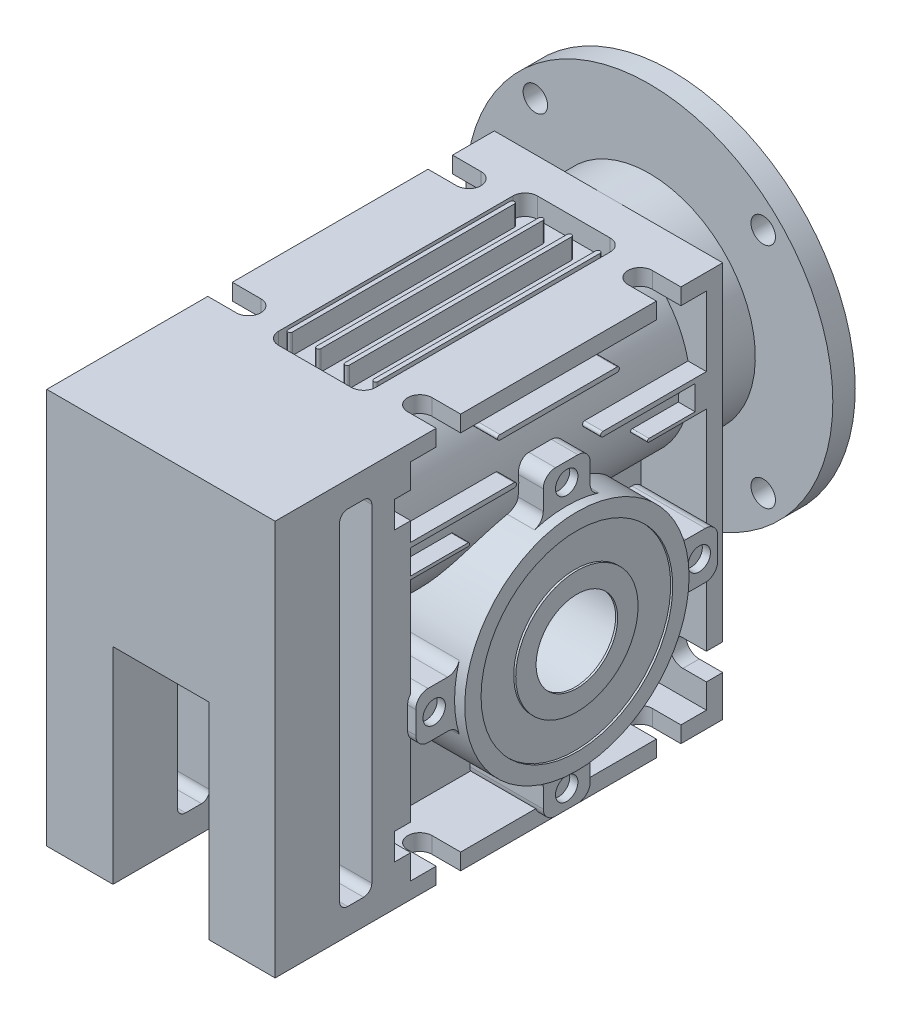
SolidWorks part; units mm, degrees
ref_plane "Front Plane" through (0, 0, 0) normal (0, 0, 1) x (1, 0, 0)
ref_plane "Top Plane" through (0, 0, 0) normal (0, 1, 0) x (1, 0, 0)
ref_plane "Right Plane" through (0, 0, 0) normal (1, 0, 0) x (0, 0, -1)
sketch "Sketch1" plane through (0, 0, 0) normal (1, 0, 0) x (0, 0, -1)
  line L1 (-40.25, -48.5) -> (40.25, -48.5)
  line L2 (-40.25, -48.5) -> (-40.25, 48.5)
  line L3 (-40.25, 48.5) -> (40.25, 48.5)
  line L4 (40.25, -48.5) -> (40.25, 48.5)
  line L5 (-40.25, -48.5) -> (40.25, 48.5) construction
  line L6 (-40.25, 48.5) -> (40.25, -48.5) construction
  point P0 (0, 0)
  dimension "D1" = 97
  dimension "D2" = 80.5
extrude "Boss-Extrude1" add sketch "Sketch1" along normal mid plane 56
sketch "Sketch2" plane through (0, 0, 0) normal (1, 0, 0) x (0, 0, -1)
  line L0 (-40.25, -48.5) -> (40.25, -48.5) construction
  circle A0 centre (0, -9.5) radius 27.5
  point P2 (0, -37)
  dimension "D2" = 55
  dimension "D1" = 11.5
extrude "Boss-Extrude2" add sketch "Sketch2" along normal mid plane 65
sketch "Sketch3" plane through (28, 0, 0) normal (1, 0, 0) x (0, 0, -1)
  line L0 (-29.2179, -15.25) -> (-34, -15.25)
  line L2 (-5.75, -38.7179) -> (-5.75, -43.5)
  line L3 (-2.75, -46.5) -> (2.75, -46.5)
  line L4 (5.75, -38.7179) -> (5.75, -43.5)
  line L5 (-5.75, 27.5) -> (5.75, -46.5) construction
  line L6 (-5.75, -46.5) -> (5.75, 27.5) construction
  line L7 (-37, -6.75) -> (-37, -12.25)
  line L8 (-29.2179, -3.75) -> (-34, -3.75)
  line L9 (-5.75, 19.7179) -> (-5.75, 24.5)
  line L10 (2.75, 27.5) -> (-2.75, 27.5)
  line L11 (5.75, 19.7179) -> (5.75, 24.5)
  line L12 (29.2179, -3.75) -> (34, -3.75)
  line L13 (37, -12.25) -> (37, -6.75)
  line L14 (29.2179, -15.25) -> (34, -15.25)
  arc A0 (-5.75, -43.5) -> (-2.75, -46.5) centre (-2.75, -43.5) ccw
  circle A1 centre (0, -9.5) radius 27.5
  arc A2 (7.8893, -35.844) -> (-7.8893, -35.844) centre (0, -9.5) ccw
  arc A3 (2.75, -46.5) -> (5.75, -43.5) centre (2.75, -43.5) ccw
  arc A4 (7.8893, -35.844) -> (5.75, -38.7179) centre (8.75, -38.7179) ccw
  arc A5 (-7.8893, -35.844) -> (-5.75, -38.7179) centre (-8.75, -38.7179) cw
  circle A6 centre (0, -42) radius 2.75
  arc A7 (-26.344, -17.3893) -> (-29.2179, -15.25) centre (-29.2179, -18.25) ccw
  arc A8 (-37, -12.25) -> (-34, -15.25) centre (-34, -12.25) ccw
  arc A9 (-34, -3.75) -> (-37, -6.75) centre (-34, -6.75) ccw
  arc A10 (-26.344, -1.6107) -> (-29.2179, -3.75) centre (-29.2179, -0.75) cw
  circle A11 centre (-32.5, -9.5) radius 2.75
  arc A12 (-7.8893, 16.844) -> (-5.75, 19.7179) centre (-8.75, 19.7179) ccw
  arc A13 (-2.75, 27.5) -> (-5.75, 24.5) centre (-2.75, 24.5) ccw
  arc A14 (5.75, 24.5) -> (2.75, 27.5) centre (2.75, 24.5) ccw
  arc A15 (7.8893, 16.844) -> (5.75, 19.7179) centre (8.75, 19.7179) cw
  circle A16 centre (0, 23) radius 2.75
  arc A17 (26.344, -1.6107) -> (29.2179, -3.75) centre (29.2179, -0.75) ccw
  arc A18 (37, -6.75) -> (34, -3.75) centre (34, -6.75) ccw
  arc A19 (34, -15.25) -> (37, -12.25) centre (34, -12.25) ccw
  arc A20 (26.344, -17.3893) -> (29.2179, -15.25) centre (29.2179, -18.25) cw
  circle A21 centre (32.5, -9.5) radius 2.75
  point P65 (0, -9.5)
  circle M5 centre (0, -9.5) radius 27.5
  dimension "D4" = 3
  dimension "D5" = 3
  dimension "D6" = 3
  dimension "D7" = 5.5
  dimension "D2" = 11.5
  dimension "D3" = 37
  dimension "D8" = 32.5
  dimension "D9" = 5.75
  dimension "D1" = 0
  dimension "D10" = 4
extrude "Boss-Extrude3" add sketch "Sketch3" along normal blind 2 contours A2 A10 L8 A9 L7 A8 L0 A7 A11 | A2 A15 L11 A14 L10 A13 L9 A12 A16 | A2 A20 L14 A19 L13 A18 L12 A17 A21 | A5 L2 A0 L3 A3 L4 A4 A6 M5 region at (28, -15.0596, 31.609) region at (28, -37.1904, 0) region at (28, 17.8129, 6.1908) region at (28, -13.5144, -27.3979)
mirror "Mirror1" about plane through (0, 0, 0) normal (1, 0, 0) of "Boss-Extrude3"
sketch "Sketch4" plane through (0, 0, -40.25) normal (0, 0, -1) x (-1, 0, 0)
  line L0 (-28, 48.5) -> (28, 48.5) construction
  circle A0 centre (0, 22.5) radius 26
  dimension "D1" = 52
extrude "Boss-Extrude4" add sketch "Sketch4" along normal blind 10
sketch "Sketch7" plane through (0, 0, -50.25) normal (0, 0, -1) x (-1, 0, 0)
  circle A0 centre (0, 22.5) radius 45
  dimension "D1" = 90
extrude "Boss-Extrude5" add sketch "Sketch7" along normal blind 5.5
sketch "Sketch8" plane through (0, 0, 0) normal (1, 0, 0) x (0, 0, -1)
  line L0 (55.75, 53) -> (52.75, 53)
  line L1 (55.75, -22.5) -> (55.75, 67.5) construction
  line L2 (52.75, 53) -> (52.75, 46.5)
  line L3 (52.75, 46.5) -> (45.75, 46.5)
  line L4 (45.75, 46.5) -> (45.75, 32.5)
  line L5 (45.75, 32.5) -> (50.75, 32.5)
  line L6 (50.75, 32.5) -> (50.75, 28)
  line L7 (50.75, 28) -> (22.75, 28)
  line L8 (22.75, 28) -> (22.75, 22.5)
  line L9 (22.75, 22.5) -> (55.75, 22.5)
  line L10 (55.75, 22.5) -> (55.75, 53)
  line L11 (55.75, 67.5) -> (50.25, 67.5) construction
  dimension "D1" = 14.5
  dimension "D2" = 3
  dimension "D3" = 7
  dimension "D4" = 24
  dimension "D5" = 5.5
  dimension "D6" = 28
  dimension "D7" = 5
  dimension "D8" = 10
revolve "Cut-Revolve1" cut sketch "Sketch8" angle 360 about L9
sketch "Sketch9" plane through (0, 0, -55.75) normal (0, 0, -1) x (-1, 0, 0)
  line L0 (0, 22.5) -> (0, 67.5) construction
  line L1 (0, 22.5) -> (27.9307, 50.4307) construction
  circle A2 centre (27.9307, 50.4307) radius 3
  circle A3 centre (27.9307, -5.4307) radius 3
  circle A4 centre (-27.9307, -5.4307) radius 3
  circle A5 centre (-27.9307, 50.4307) radius 3
  circle A6 centre (0, 22.5) radius 45 construction
  point P18 (0, 22.5)
  dimension "D1" = 6
  dimension "D3" = 45
  dimension "D4" = 39.5
  dimension "D2" = 4
extrude "Cut-Extrude1" cut sketch "Sketch9" against normal blind 5.5 contours A2 | A3 | A4 | A5
sketch "Sketch10" plane through (-28, 0, 0) normal (-1, 0, 0) x (0, 0, 1)
  line L4 (-40.25, 48.5) -> (-40.25, -48.5)
  line L5 (-40.25, -48.5) -> (40.25, -48.5)
  line L6 (40.25, -48.5) -> (40.25, 48.5)
  line L7 (40.25, 48.5) -> (-40.25, 48.5)
  line L8 (-40.25, 48.5) -> (-40.25, -48.5)
  line L9 (-40.25, -48.5) -> (40.25, -48.5)
  line L10 (40.25, -48.5) -> (40.25, 48.5)
  line L11 (40.25, 48.5) -> (-40.25, 48.5)
  line L12 (29.2179, -3.75) -> (34, -3.75) construction
  line L13 (37, -6.75) -> (37, -12.25) construction
  line L14 (29.2179, -15.25) -> (34, -15.25) construction
  line L15 (5.75, -38.7179) -> (5.75, -43.5) construction
  line L16 (2.75, -46.5) -> (-2.75, -46.5) construction
  line L17 (-5.75, -38.7179) -> (-5.75, -43.5) construction
  line L18 (-29.2179, -15.25) -> (-34, -15.25) construction
  line L19 (-37, -12.25) -> (-37, -6.75) construction
  line L20 (-29.2179, -3.75) -> (-34, -3.75) construction
  line L21 (-5.75, 19.7179) -> (-5.75, 24.5) construction
  line L22 (-2.75, 27.5) -> (2.75, 27.5) construction
  line L23 (5.75, 19.7179) -> (5.75, 24.5) construction
  line L24 (29.2179, -3.75) -> (34, -3.75)
  line L25 (37, -6.75) -> (37, -12.25)
  line L26 (29.2179, -15.25) -> (34, -15.25)
  line L27 (5.75, -38.7179) -> (5.75, -43.5)
  line L28 (2.75, -46.5) -> (-2.75, -46.5)
  line L29 (-5.75, -38.7179) -> (-5.75, -43.5)
  line L30 (-29.2179, -15.25) -> (-34, -15.25)
  line L31 (-37, -12.25) -> (-37, -6.75)
  line L32 (-29.2179, -3.75) -> (-34, -3.75)
  line L33 (-5.75, 19.7179) -> (-5.75, 24.5)
  line L34 (-2.75, 27.5) -> (2.75, 27.5)
  line L35 (5.75, 19.7179) -> (5.75, 24.5)
  line L36 (36.25, 44.5) -> (-36.25, 44.5)
  line L37 (-36.25, 44.5) -> (-36.25, -44.5)
  line L38 (-36.25, -44.5) -> (36.25, -44.5)
  line L39 (36.25, -44.5) -> (36.25, 44.5)
  line L40 (-14.3534, 38.7414) -> (14.3534, 38.7414) construction
  line L41 (-14.3534, 39.3275) -> (14.3534, 39.3275)
  line L42 (-14.3534, 38.1553) -> (14.3534, 38.1553)
  line L43 (-10.8913, 26.8155) -> (-36.25, 26.8155) construction
  line L44 (-10.8913, 26.2345) -> (-36.25, 26.2345)
  line L45 (-10.8913, 27.3965) -> (-36.25, 27.3965)
  line L46 (-22.1859, 19.851) -> (-36.25, 19.851) construction
  line L47 (-22.1859, 19.4507) -> (-36.25, 19.4507)
  line L48 (-22.1859, 20.2512) -> (-36.25, 20.2512)
  line L49 (0, 25.75) -> (0, 0)
  line L50 (36.25, 44.5) -> (36.25, -44.5)
  line L51 (22.1859, 19.851) -> (36.25, 19.851) construction
  line L52 (22.1859, 19.4507) -> (36.25, 19.4507)
  line L53 (22.1859, 20.2512) -> (36.25, 20.2512)
  line L54 (10.8913, 26.8155) -> (36.25, 26.8155) construction
  line L55 (10.8913, 26.2345) -> (36.25, 26.2345)
  line L56 (10.8913, 27.3965) -> (36.25, 27.3965)
  line L57 (-33.4862, 26.2345) -> (-33.4862, 20.2512)
  arc A0 (26.344, -1.6107) -> (29.2179, -3.75) centre (29.2179, -0.75) ccw construction
  arc A1 (37, -6.75) -> (34, -3.75) centre (34, -6.75) ccw construction
  arc A2 (34, -15.25) -> (37, -12.25) centre (34, -12.25) ccw construction
  arc A3 (29.2179, -15.25) -> (26.344, -17.3893) centre (29.2179, -18.25) ccw construction
  arc A4 (7.8893, -35.844) -> (26.344, -17.3893) centre (0, -9.5) ccw construction
  arc A5 (7.8893, -35.844) -> (5.75, -38.7179) centre (8.75, -38.7179) ccw construction
  arc A6 (2.75, -46.5) -> (5.75, -43.5) centre (2.75, -43.5) ccw construction
  arc A7 (-5.75, -43.5) -> (-2.75, -46.5) centre (-2.75, -43.5) ccw construction
  arc A8 (-5.75, -38.7179) -> (-7.8893, -35.844) centre (-8.75, -38.7179) ccw construction
  arc A9 (-26.344, -17.3893) -> (-7.8893, -35.844) centre (0, -9.5) ccw construction
  arc A10 (-26.344, -17.3893) -> (-29.2179, -15.25) centre (-29.2179, -18.25) ccw construction
  arc A11 (-37, -12.25) -> (-34, -15.25) centre (-34, -12.25) ccw construction
  arc A12 (-34, -3.75) -> (-37, -6.75) centre (-34, -6.75) ccw construction
  arc A13 (-29.2179, -3.75) -> (-26.344, -1.6107) centre (-29.2179, -0.75) ccw construction
  arc A14 (-7.8893, 16.844) -> (-26.344, -1.6107) centre (0, -9.5) ccw construction
  arc A15 (-7.8893, 16.844) -> (-5.75, 19.7179) centre (-8.75, 19.7179) ccw construction
  arc A16 (-2.75, 27.5) -> (-5.75, 24.5) centre (-2.75, 24.5) ccw construction
  arc A17 (5.75, 24.5) -> (2.75, 27.5) centre (2.75, 24.5) ccw construction
  arc A18 (5.75, 19.7179) -> (7.8893, 16.844) centre (8.75, 19.7179) ccw construction
  arc A19 (26.344, -1.6107) -> (7.8893, 16.844) centre (0, -9.5) ccw construction
  arc A20 (26.344, -1.6107) -> (29.2179, -3.75) centre (29.2179, -0.75) ccw
  arc A21 (37, -6.75) -> (34, -3.75) centre (34, -6.75) ccw
  arc A22 (34, -15.25) -> (37, -12.25) centre (34, -12.25) ccw
  arc A23 (29.2179, -15.25) -> (26.344, -17.3893) centre (29.2179, -18.25) ccw
  arc A24 (7.8893, -35.844) -> (26.344, -17.3893) centre (0, -9.5) ccw
  arc A25 (7.8893, -35.844) -> (5.75, -38.7179) centre (8.75, -38.7179) ccw
  arc A26 (2.75, -46.5) -> (5.75, -43.5) centre (2.75, -43.5) ccw
  arc A27 (-5.75, -43.5) -> (-2.75, -46.5) centre (-2.75, -43.5) ccw
  arc A28 (-5.75, -38.7179) -> (-7.8893, -35.844) centre (-8.75, -38.7179) ccw
  arc A29 (-26.344, -17.3893) -> (-7.8893, -35.844) centre (0, -9.5) ccw
  arc A30 (-26.344, -17.3893) -> (-29.2179, -15.25) centre (-29.2179, -18.25) ccw
  arc A31 (-37, -12.25) -> (-34, -15.25) centre (-34, -12.25) ccw
  arc A32 (-34, -3.75) -> (-37, -6.75) centre (-34, -6.75) ccw
  arc A33 (-29.2179, -3.75) -> (-26.344, -1.6107) centre (-29.2179, -0.75) ccw
  arc A34 (-7.8893, 16.844) -> (-26.344, -1.6107) centre (0, -9.5) ccw
  arc A35 (-7.8893, 16.844) -> (-5.75, 19.7179) centre (-8.75, 19.7179) ccw
  arc A36 (-2.75, 27.5) -> (-5.75, 24.5) centre (-2.75, 24.5) ccw
  arc A37 (5.75, 24.5) -> (2.75, 27.5) centre (2.75, 24.5) ccw
  arc A38 (5.75, 19.7179) -> (7.8893, 16.844) centre (8.75, 19.7179) ccw
  arc A39 (26.344, -1.6107) -> (7.8893, 16.844) centre (0, -9.5) ccw
  arc A40 (-14.3534, 39.3275) -> (-14.3534, 38.1553) centre (-14.3534, 38.7414) ccw
  arc A41 (14.3534, 38.1553) -> (14.3534, 39.3275) centre (14.3534, 38.7414) ccw
  arc A42 (-10.8913, 26.2345) -> (-10.8913, 27.3965) centre (-10.8913, 26.8155) ccw
  arc A43 (-36.25, 27.3965) -> (-36.25, 26.2345) centre (-36.25, 26.8155) ccw
  arc A44 (-22.1859, 19.4507) -> (-22.1859, 20.2512) centre (-22.1859, 19.851) ccw
  arc A45 (-36.25, 20.2512) -> (-36.25, 19.4507) centre (-36.25, 19.851) ccw
  circle A46 centre (0, 23) radius 2.75 construction
  circle A47 centre (0, 23) radius 2.75 construction
  arc A48 (22.1859, 19.4507) -> (22.1859, 20.2512) centre (22.1859, 19.851) cw
  arc A49 (36.25, 20.2512) -> (36.25, 19.4507) centre (36.25, 19.851) cw
  arc A50 (10.8913, 26.2345) -> (10.8913, 27.3965) centre (10.8913, 26.8155) cw
  arc A51 (36.25, 27.3965) -> (36.25, 26.2345) centre (36.25, 26.8155) cw
  point P59 (0, 38.7414)
  point P66 (-23.5706, 26.8155)
  point P73 (-29.2179, 19.851)
  point P87 (29.2179, 19.851)
  point P94 (23.5706, 26.8155)
  point P111 (0, 44.5)
  line M5 (-5.75, -43.5) -> (-5.75, -38.7179)
  arc M6 (-5.75, -38.7179) -> (-7.8893, -35.844) centre (-8.75, -38.7179) ccw
  arc M7 (-7.8893, -35.844) -> (-26.344, -17.3893) centre (0, -9.5) cw
  arc M8 (-26.344, -17.3893) -> (-29.2179, -15.25) centre (-29.2179, -18.25) ccw
  line M9 (-29.2179, -15.25) -> (-34, -15.25)
  arc M10 (-34, -15.25) -> (-37, -12.25) centre (-34, -12.25) cw
  arc M12 (-37, -6.75) -> (-34, -3.75) centre (-34, -6.75) cw
  line M13 (-34, -3.75) -> (-29.2179, -3.75)
  arc M14 (-29.2179, -3.75) -> (-26.344, -1.6107) centre (-29.2179, -0.75) ccw
  arc M15 (-26.344, -1.6107) -> (-7.8893, 16.844) centre (0, -9.5) cw
  arc M16 (-7.8893, 16.844) -> (-5.75, 19.7179) centre (-8.75, 19.7179) ccw
  line M17 (-5.75, 19.7179) -> (-5.75, 24.5)
  arc M18 (-5.75, 24.5) -> (-2.75, 27.5) centre (-2.75, 24.5) cw
  line M19 (-2.75, 27.5) -> (2.75, 27.5)
  arc M20 (2.75, 27.5) -> (5.75, 24.5) centre (2.75, 24.5) cw
  line M21 (5.75, 24.5) -> (5.75, 19.7179)
  arc M22 (5.75, 19.7179) -> (7.8893, 16.844) centre (8.75, 19.7179) ccw
  arc M23 (7.8893, 16.844) -> (26.344, -1.6107) centre (0, -9.5) cw
  arc M24 (26.344, -1.6107) -> (29.2179, -3.75) centre (29.2179, -0.75) ccw
  line M25 (29.2179, -3.75) -> (34, -3.75)
  arc M26 (34, -3.75) -> (37, -6.75) centre (34, -6.75) cw
  arc M28 (37, -12.25) -> (34, -15.25) centre (34, -12.25) cw
  line M29 (34, -15.25) -> (29.2179, -15.25)
  arc M30 (29.2179, -15.25) -> (26.344, -17.3893) centre (29.2179, -18.25) ccw
  arc M31 (26.344, -17.3893) -> (7.8893, -35.844) centre (0, -9.5) cw
  arc M32 (7.8893, -35.844) -> (5.75, -38.7179) centre (8.75, -38.7179) ccw
  line M33 (5.75, -38.7179) -> (5.75, -43.5)
  arc M34 (5.75, -43.5) -> (2.75, -46.5) centre (2.75, -43.5) cw
  arc M36 (-2.75, -46.5) -> (-5.75, -43.5) centre (-2.75, -43.5) cw
  dimension "D1" = 0
  dimension "D2" = 4
extrude "Cut-Extrude2" cut sketch "Sketch10" against normal blind 16 contours L39 L36 L37 M26 M12 M13 M14 M15 M16 M17 M18 M19 M20 M21 M22 M23 M24 M25 | L38 L39 M28 M29 M30 M31 M32 M33 M34 | L37 L38 M36 M5 M6 M7 M8 M9 M10 region at (-28, -2.4533, 27.95) region at (-28, -33.2355, 24.7344) region at (-28, -33.2355, -24.7344)
sketch "Sketch11" plane through (-32.5, 0, 0) normal (-1, 0, 0) x (0, 0, 1)
  circle A0 centre (0, -9.5) radius 15
  circle A1 centre (0, -9.5) radius 27.5
  circle A2 centre (0, -9.5) radius 27.5
  circle A3 centre (0, -9.5) radius 10
  circle A4 centre (0, -9.5) radius 23.5
  dimension "D2" = 30
  dimension "D3" = 20
  dimension "D1" = 0
  dimension "D4" = 4
extrude "Cut-Extrude3" cut sketch "Sketch11" against normal blind 0.5 contours A4 A0 region at (-32.5, -9.5, -22.8353)
extrude "Cut-Extrude4" cut sketch "Sketch11<3>" against normal blind 75 contours A3
sketch "Sketch11<3>" plane through (-32.5, 0, 0) normal (-1, 0, 0) x (0, 0, 1) same geometry as "Sketch11"
mirror "Mirror3" about plane through (0, 0, 0) normal (1, 0, 0) of "Cut-Extrude3", "Cut-Extrude2"
sketch "Sketch12" plane through (0, 0, -45.75) normal (0, 0, -1) x (-1, 0, 0)
  circle A1 centre (0, 22.5) radius 24
  circle A2 centre (0, 22.5) radius 24
  dimension "D1" = 0
extrude "Boss-Extrude6" add sketch "Sketch12" against normal blind 85
sketch "Sketch13" plane through (0, 0, 40.25) normal (0, 0, 1) x (1, 0, 0)
  line L0 (33.75, 35.25) -> (22.25, 35.25) construction
  line L1 (28, 48.5) -> (28, -48.5) construction
  line L2 (33.75, 32) -> (22.25, 32)
  line L3 (33.75, 38.5) -> (22.25, 38.5)
  line L4 (0, 48.5) -> (0, 0)
  line L5 (28, 48.5) -> (-28, 48.5) construction
  line L6 (0, 0) -> (28, 0)
  line L7 (-33.75, 35.25) -> (-22.25, 35.25) construction
  line L8 (-33.75, 32) -> (-22.25, 32)
  line L9 (-33.75, 38.5) -> (-22.25, 38.5)
  line L10 (-33.75, -35.25) -> (-22.25, -35.25) construction
  line L11 (-33.75, -32) -> (-22.25, -32)
  line L12 (-33.75, -38.5) -> (-22.25, -38.5)
  line L13 (33.75, -35.25) -> (22.25, -35.25) construction
  line L14 (33.75, -32) -> (22.25, -32)
  line L15 (33.75, -38.5) -> (22.25, -38.5)
  arc A0 (33.75, 32) -> (33.75, 38.5) centre (33.75, 35.25) ccw
  arc A1 (22.25, 38.5) -> (22.25, 32) centre (22.25, 35.25) ccw
  arc A2 (-33.75, 32) -> (-33.75, 38.5) centre (-33.75, 35.25) cw
  arc A3 (-22.25, 38.5) -> (-22.25, 32) centre (-22.25, 35.25) cw
  arc A4 (-33.75, -32) -> (-33.75, -38.5) centre (-33.75, -35.25) ccw
  arc A5 (-22.25, -38.5) -> (-22.25, -32) centre (-22.25, -35.25) ccw
  arc A6 (33.75, -32) -> (33.75, -38.5) centre (33.75, -35.25) cw
  arc A7 (22.25, -38.5) -> (22.25, -32) centre (22.25, -35.25) cw
  point P4 (28, 35.25)
  point P14 (19, 35.25)
  point P18 (-28, 35.25)
  point P25 (-28, -35.25)
  point P32 (28, -35.25)
  line M5 (-28, 48.5) -> (-28, -48.5)
  line M7 (28, -48.5) -> (28, 48.5)
  dimension "D1" = 6.5
  dimension "D2" = 9
  dimension "D3" = 10
extrude "Cut-Extrude5" cut sketch "Sketch13" against normal blind 5 contours A3 L9 L8 M5 | L3 A1 L2 M7 | A7 L15 L14 M7 | L12 A5 L11 M5 region at (23.817, -35.25, 40.25) region at (23.817, 35.25, 40.25) region at (-23.817, -35.25, 40.25) region at (-23.817, 35.25, 40.25)
sketch "Sketch14" plane through (0, 0, 40.25) normal (0, 0, 1) x (1, 0, 0)
  line L0 (-6.8533, -95.7506) -> (-6.8533, -1.2494) construction
  line L1 (28, -48.5) -> (-28, -48.5) construction
  line L2 (-7.5206, -95.7506) -> (-7.5206, -1.2494)
  line L3 (-6.186, -95.7506) -> (-6.186, -1.2494)
  line L4 (0.1467, -95.7506) -> (0.1467, -1.2494) construction
  line L5 (-0.5206, -95.7506) -> (-0.5206, -1.2494)
  line L6 (0.814, -95.7506) -> (0.814, -1.2494)
  line L7 (7.1467, -95.7506) -> (7.1467, -1.2494) construction
  line L8 (6.4794, -95.7506) -> (6.4794, -1.2494)
  line L9 (7.814, -95.7506) -> (7.814, -1.2494)
  line L11 (-11.7616, -98.9853) -> (11.7616, -98.9853)
  line L12 (-11.7616, -98.9853) -> (-11.7616, 1.9853)
  line L13 (-11.7616, 1.9853) -> (11.7616, 1.9853)
  line L14 (11.7616, -98.9853) -> (11.7616, 1.9853)
  line L15 (-11.7616, -98.9853) -> (11.7616, 1.9853) construction
  line L16 (-11.7616, 1.9853) -> (11.7616, -98.9853) construction
  circle A0 centre (0, 22.5) radius 16.9727
  arc A1 (-7.5206, -95.7506) -> (-6.186, -95.7506) centre (-6.8533, -95.7506) ccw
  arc A2 (-6.186, -1.2494) -> (-7.5206, -1.2494) centre (-6.8533, -1.2494) ccw
  arc A3 (-0.5206, -95.7506) -> (0.814, -95.7506) centre (0.1467, -95.7506) ccw
  arc A4 (0.814, -1.2494) -> (-0.5206, -1.2494) centre (0.1467, -1.2494) ccw
  arc A5 (6.4794, -95.7506) -> (7.814, -95.7506) centre (7.1467, -95.7506) ccw
  arc A6 (7.814, -1.2494) -> (6.4794, -1.2494) centre (7.1467, -1.2494) ccw
  point P7 (-6.8533, -48.5)
  point P12 (0, -48.5)
  point P16 (0.1467, -48.5)
  point P23 (7.1467, -48.5)
  dimension "D1" = 3
extrude "Cut-Extrude7" cut sketch "Sketch14" against normal blind 25 contours A6 L9 A1 L14 L13 L12 L2 A2 L3 L5 A4 L6 L8 region at (-10.7249, -48.5, 40.25)
sketch "Sketch15" plane through (0, -48.5, 0) normal (0, -1, 0) x (1, 0, 0)
  line L0 (-6.8533, 117.6108) -> (-6.8533, -37.1108) construction
  line L1 (-6.186, 40.25) -> (-7.5206, 40.25) construction
  line L2 (-6.186, 117.6108) -> (-6.186, -37.1108)
  line L3 (-7.5206, 117.6108) -> (-7.5206, -37.1108)
  line L4 (-6.186, 15.25) -> (-6.186, 40.25) construction
  line L5 (0.1467, 117.6108) -> (0.1467, -37.1108) construction
  line L6 (0.814, 117.6108) -> (0.814, -37.1108)
  line L7 (-0.5206, 117.6108) -> (-0.5206, -37.1108)
  line L8 (7.1467, 117.6108) -> (7.1467, -37.1108) construction
  line L9 (7.814, 117.6108) -> (7.814, -37.1108)
  line L10 (6.4794, 117.6108) -> (6.4794, -37.1108)
  line L11 (-11.7616, 40.25) -> (11.7616, 40.25) construction
  line L12 (-11.7616, 120.75) -> (11.7616, 120.75)
  line L13 (-11.7616, 120.75) -> (-11.7616, -40.25)
  line L14 (-11.7616, -40.25) -> (11.7616, -40.25)
  line L15 (11.7616, 120.75) -> (11.7616, -40.25)
  line L16 (-11.7616, 120.75) -> (11.7616, -40.25) construction
  line L17 (-11.7616, -40.25) -> (11.7616, 120.75) construction
  line L18 (28, -40.25) -> (-28, -40.25) construction
  arc A0 (-6.186, 117.6108) -> (-7.5206, 117.6108) centre (-6.8533, 117.6108) ccw
  arc A1 (-7.5206, -37.1108) -> (-6.186, -37.1108) centre (-6.8533, -37.1108) ccw
  arc A2 (0.814, 117.6108) -> (-0.5206, 117.6108) centre (0.1467, 117.6108) ccw
  arc A3 (-0.5206, -37.1108) -> (0.814, -37.1108) centre (0.1467, -37.1108) ccw
  arc A4 (7.814, 117.6108) -> (6.4794, 117.6108) centre (7.1467, 117.6108) ccw
  arc A5 (6.4794, -37.1108) -> (7.814, -37.1108) centre (7.1467, -37.1108) ccw
  point P4 (-6.8533, 40.25)
  point P12 (0, 40.25)
  point P14 (0.1467, 40.25)
  point P21 (7.1467, 40.25)
  dimension "D1" = 3
extrude "Cut-Extrude8" cut sketch "Sketch15" against normal blind 25
sketch "Sketch16" plane through (-32, 0, 0) normal (-1, 0, 0) x (0, 0, 1)
  circle A0 centre (0, -9.5) radius 27.5
extrude "Boss-Extrude7" add sketch "Sketch16" against normal blind 55
sketch "Sketch17" plane through (0, 0, -40.25) normal (0, 0, -1) x (-1, 0, 0)
  line L0 (0, 48.5) -> (0, 0) construction
  line L1 (0, 0) -> (-28, 0) construction
  line L2 (-33.75, 32) -> (-22.25, 32)
  line L3 (-22.25, 38.5) -> (-33.75, 38.5)
  line L4 (-33.75, 32) -> (-22.25, 32)
  line L5 (-22.25, 38.5) -> (-33.75, 38.5)
  line L6 (33.75, -32) -> (22.25, -32)
  line L7 (22.25, -38.5) -> (33.75, -38.5)
  line L8 (33.75, -32) -> (22.25, -32)
  line L9 (22.25, -38.5) -> (33.75, -38.5)
  line L10 (22.25, 32) -> (33.75, 32)
  line L11 (33.75, 38.5) -> (22.25, 38.5)
  line L12 (22.25, 32) -> (33.75, 32)
  line L13 (33.75, 38.5) -> (22.25, 38.5)
  line L14 (-22.25, -32) -> (-33.75, -32)
  line L15 (-33.75, -38.5) -> (-22.25, -38.5)
  line L16 (-22.25, -32) -> (-33.75, -32)
  line L17 (-33.75, -38.5) -> (-22.25, -38.5)
  line L18 (0, 48.5) -> (0, 0)
  line L19 (0, 0) -> (-28, 0)
  arc A2 (-22.25, 32) -> (-22.25, 38.5) centre (-22.25, 35.25) ccw
  arc A3 (-33.75, 38.5) -> (-33.75, 32) centre (-33.75, 35.25) ccw
  arc A4 (-22.25, 32) -> (-22.25, 38.5) centre (-22.25, 35.25) ccw
  arc A5 (-33.75, 38.5) -> (-33.75, 32) centre (-33.75, 35.25) ccw
  arc A6 (22.25, -32) -> (22.25, -38.5) centre (22.25, -35.25) ccw
  arc A7 (33.75, -38.5) -> (33.75, -32) centre (33.75, -35.25) ccw
  arc A8 (22.25, -32) -> (22.25, -38.5) centre (22.25, -35.25) ccw
  arc A9 (33.75, -38.5) -> (33.75, -32) centre (33.75, -35.25) ccw
  arc A10 (22.25, 38.5) -> (22.25, 32) centre (22.25, 35.25) ccw
  arc A11 (33.75, 32) -> (33.75, 38.5) centre (33.75, 35.25) ccw
  arc A12 (22.25, 38.5) -> (22.25, 32) centre (22.25, 35.25) ccw
  arc A13 (33.75, 32) -> (33.75, 38.5) centre (33.75, 35.25) ccw
  arc A14 (-22.25, -38.5) -> (-22.25, -32) centre (-22.25, -35.25) ccw
  arc A15 (-33.75, -32) -> (-33.75, -38.5) centre (-33.75, -35.25) ccw
  arc A16 (-22.25, -38.5) -> (-22.25, -32) centre (-22.25, -35.25) ccw
  arc A17 (-33.75, -32) -> (-33.75, -38.5) centre (-33.75, -35.25) ccw
  line M22 (28, -48.5) -> (28, 48.5)
  line M26 (-28, 48.5) -> (-28, -48.5)
  dimension "D1" = 0
  dimension "D2" = 0
  dimension "D3" = 0
  dimension "D4" = 0
extrude "Cut-Extrude9" cut sketch "Sketch17" against normal blind 5 contours L8 A8 L9 M22 | L17 A16 L16 M26 region at (23.817, -35.25, -40.25) region at (-23.817, -35.25, -40.25)
sketch "Sketch18" plane through (0, -48.5, 0) normal (0, -1, 0) x (1, 0, 0)
  line L0 (35, 27) -> (21, 27) construction
  line L1 (28, 40.25) -> (28, -40.25) construction
  line L2 (35, 24) -> (21, 24)
  line L3 (35, 30) -> (21, 30)
  line L4 (0, 0) -> (0, 56.7479)
  line L5 (0, 0) -> (55.9398, 0)
  line L6 (-35, 27) -> (-21, 27) construction
  line L7 (-35, 24) -> (-21, 24)
  line L8 (-35, 30) -> (-21, 30)
  line L9 (-35, -27) -> (-21, -27) construction
  line L10 (-35, -24) -> (-21, -24)
  line L11 (-35, -30) -> (-21, -30)
  line L12 (35, -27) -> (21, -27) construction
  line L13 (35, -24) -> (21, -24)
  line L14 (35, -30) -> (21, -30)
  arc A0 (35, 24) -> (35, 30) centre (35, 27) ccw
  arc A1 (21, 30) -> (21, 24) centre (21, 27) ccw
  arc A2 (-35, 24) -> (-35, 30) centre (-35, 27) cw
  arc A3 (-21, 30) -> (-21, 24) centre (-21, 27) cw
  arc A4 (-35, -24) -> (-35, -30) centre (-35, -27) ccw
  arc A5 (-21, -30) -> (-21, -24) centre (-21, -27) ccw
  arc A6 (35, -24) -> (35, -30) centre (35, -27) cw
  arc A7 (21, -30) -> (21, -24) centre (21, -27) cw
  point P4 (28, 27)
  point P15 (-28, 27)
  point P22 (-28, -27)
  point P29 (28, -27)
  point P34 (18, 27)
  dimension "D1" = 6
  dimension "D2" = 48
  dimension "D3" = 10
extrude "Cut-Extrude10" cut sketch "Sketch18" against normal blind 5 contours L2 A1 L3 A0 | L7 A3 L8 A2 | L10 A5 L11 A4 | L13 A7 L14 A6
sketch "Sketch19" plane through (0, 48.5, 0) normal (0, 1, 0) x (1, 0, 0)
  line L0 (0, 0) -> (0, -56.7479) construction
  line L1 (0, 0) -> (55.9398, 0) construction
  line L2 (35, -24) -> (21, -24)
  line L3 (21, -30) -> (35, -30)
  line L4 (35, -24) -> (21, -24)
  line L5 (21, -30) -> (35, -30)
  line L6 (-35, 24) -> (-21, 24)
  line L7 (-21, 30) -> (-35, 30)
  line L8 (-35, 24) -> (-21, 24)
  line L9 (-21, 30) -> (-35, 30)
  line L10 (-21, -24) -> (-35, -24)
  line L11 (-35, -30) -> (-21, -30)
  line L12 (-21, -24) -> (-35, -24)
  line L13 (-35, -30) -> (-21, -30)
  line L14 (35, 30) -> (21, 30)
  line L15 (21, 24) -> (35, 24)
  line L16 (35, 30) -> (21, 30)
  line L17 (21, 24) -> (35, 24)
  line L18 (0, 0) -> (0, -56.7479)
  line L19 (0, 0) -> (55.9398, 0)
  arc A2 (21, -24) -> (21, -30) centre (21, -27) ccw
  arc A3 (35, -30) -> (35, -24) centre (35, -27) ccw
  arc A4 (21, -24) -> (21, -30) centre (21, -27) ccw
  arc A5 (35, -30) -> (35, -24) centre (35, -27) ccw
  arc A6 (-21, 24) -> (-21, 30) centre (-21, 27) ccw
  arc A7 (-35, 30) -> (-35, 24) centre (-35, 27) ccw
  arc A8 (-21, 24) -> (-21, 30) centre (-21, 27) ccw
  arc A9 (-35, 30) -> (-35, 24) centre (-35, 27) ccw
  arc A10 (-21, -30) -> (-21, -24) centre (-21, -27) ccw
  arc A11 (-35, -24) -> (-35, -30) centre (-35, -27) ccw
  arc A12 (-21, -30) -> (-21, -24) centre (-21, -27) ccw
  arc A13 (-35, -24) -> (-35, -30) centre (-35, -27) ccw
  arc A14 (21, 30) -> (21, 24) centre (21, 27) ccw
  arc A15 (35, 24) -> (35, 30) centre (35, 27) ccw
  arc A16 (21, 30) -> (21, 24) centre (21, 27) ccw
  arc A17 (35, 24) -> (35, 30) centre (35, 27) ccw
  dimension "D1" = 0
  dimension "D2" = 0
  dimension "D3" = 0
  dimension "D4" = 0
extrude "Cut-Extrude11" cut sketch "Sketch19" against normal blind 5 contours L17 A17 L16 A16 | L5 A5 L4 A4 | L13 A12 L12 A13 | L8 A8 L9 A9
sketch "Sketch20" plane through (32.5, 0, 0) normal (1, 0, 0) x (0, 0, -1)
  circle A0 centre (0, -9.5) radius 10 construction
  circle A1 centre (0, -9.5) radius 10
extrude "Cut-Extrude12" cut sketch "Sketch20" against normal through all
sketch "Sketch21" plane through (0, 48.5, 0) normal (0, 1, 0) x (1, 0, 0)
  line L0 (-10.5772, -27.2293) -> (-10.5772, 27.2293) construction
  line L1 (-11.9262, -31.7383) -> (11.9262, -31.7383)
  line L2 (-11.9262, -31.7383) -> (-11.9262, 31.7383)
  line L3 (-11.9262, 31.7383) -> (11.9262, 31.7383)
  line L4 (11.9262, -31.7383) -> (11.9262, 31.7383)
  line L5 (-11.9262, -31.7383) -> (11.9262, 31.7383) construction
  line L6 (-11.9262, 31.7383) -> (11.9262, -31.7383) construction
  line L7 (-11.1063, -27.2293) -> (-11.1063, 27.2293)
  line L8 (-10.0481, -27.2293) -> (-10.0481, 27.2293)
  line L9 (-3.5772, -27.2293) -> (-3.5772, 27.2293) construction
  line L10 (-4.1063, -27.2293) -> (-4.1063, 27.2293)
  line L11 (-3.0481, -27.2293) -> (-3.0481, 27.2293)
  line L12 (3.4228, -27.2293) -> (3.4228, 27.2293) construction
  line L13 (2.8937, -27.2293) -> (2.8937, 27.2293)
  line L14 (3.9519, -27.2293) -> (3.9519, 27.2293)
  line L15 (10.4228, -27.2293) -> (10.4228, 27.2293) construction
  line L16 (9.8937, -27.2293) -> (9.8937, 27.2293)
  line L17 (10.9519, -27.2293) -> (10.9519, 27.2293)
  arc A0 (-11.1063, -27.2293) -> (-10.0481, -27.2293) centre (-10.5772, -27.2293) ccw
  arc A1 (-10.0481, 27.2293) -> (-11.1063, 27.2293) centre (-10.5772, 27.2293) ccw
  arc A2 (-4.1063, -27.2293) -> (-3.0481, -27.2293) centre (-3.5772, -27.2293) ccw
  arc A3 (-3.0481, 27.2293) -> (-4.1063, 27.2293) centre (-3.5772, 27.2293) ccw
  arc A4 (2.8937, -27.2293) -> (3.9519, -27.2293) centre (3.4228, -27.2293) ccw
  arc A5 (3.9519, 27.2293) -> (2.8937, 27.2293) centre (3.4228, 27.2293) ccw
  arc A6 (9.8937, -27.2293) -> (10.9519, -27.2293) centre (10.4228, -27.2293) ccw
  arc A7 (10.9519, 27.2293) -> (9.8937, 27.2293) centre (10.4228, 27.2293) ccw
  point P0 (0, 0)
  point P8 (-10.5772, 0)
  point P16 (-3.5772, 0)
  point P23 (3.4228, 0)
  point P30 (10.4228, 0)
  dimension "D1" = 4
extrude "Cut-Extrude13" cut sketch "Sketch21" against normal blind 5
fillet "Fillet1" radius 3 4 edges at (-11.9262, 46, 31.7383) (11.9262, 46, 31.7383) (11.9262, 46, -31.7383) (-11.9262, 46, -31.7383)
fillet "Fillet2" radius 8 3 edges at (7.1467, -48.5, 40.25) (0.1467, -48.5, 40.25) (-6.8533, -48.5, 40.25)
sketch "Sketch22" plane through (0, 0, -45.75) normal (0, 0, -1) x (-1, 0, 0)
  circle A0 centre (0, 22.5) radius 5.5 construction
  circle A1 centre (0, 22.5) radius 5.5
extrude "Cut-Extrude14" cut sketch "Sketch22" against normal blind 20
ref_plane "Plane1" through (-32.5, 0, 0) normal (-1, 0, 0) x (0, 0, 1)
sketch "Sketch23" plane through (-32.5, 0, 0) normal (-1, 0, 0) x (0, 0, 1)
  circle A0 centre (0, -9.5) radius 10
  dimension "D1" = 20
sketch "Sketch24" plane through (-32.5, 0, 0) normal (-1, 0, 0) x (0, 0, 1)
  circle A0 centre (0, -9.5) radius 7
ref_plane "Plane2" through (0, 0, 40.25) normal (0, 0, 1) x (1, 0, 0)
sketch "Sketch25" plane through (0, 0, 40.25) normal (0, 0, 1) x (1, 0, 0)
  line L0 (28, 48.5) -> (-28, 48.5)
  line L1 (-28, 48.5) -> (-28, -48.5)
  line L2 (-28, -48.5) -> (-11.7616, -48.5)
  line L3 (-11.7616, -48.5) -> (-11.7616, 1.9853)
  line L4 (-11.7616, 1.9853) -> (11.7616, 1.9853)
  line L5 (11.7616, 1.9853) -> (11.7616, -48.5)
  line L6 (11.7616, -48.5) -> (28, -48.5)
  line L7 (28, -48.5) -> (28, 48.5)
  line L8 (28, 48.5) -> (28.451, 48.5922)
extrude "Boss-Extrude8" add sketch "Sketch25" along normal blind 29.24 contours L0 L1 L2 L3 L4 L5 L6 L7
sketch "Sketch28" plane through (28, 0, 0) normal (1, 0, 0) x (0, 0, -1)
  line L0 (-49.745, 0) -> (-69.49, 48.5) construction
  line L1 (-69.49, 48.5) -> (-30, 48.5) construction
  line L2 (-49.745, 0) -> (-69.49, -48.5) construction
  line L4 (-45.7908, -42.2067) -> (-53.6992, -42.2067)
  line L5 (-45.7908, -42.2067) -> (-45.7908, 42.2067)
  line L6 (-45.7908, 42.2067) -> (-53.6992, 42.2067)
  line L7 (-53.6992, -42.2067) -> (-53.6992, 42.2067)
  line L8 (-45.7908, -42.2067) -> (-53.6992, 42.2067) construction
  line L9 (-45.7908, 42.2067) -> (-53.6992, -42.2067) construction
extrude "Cut-Extrude15" cut sketch "Sketch28" against normal blind 102.24
fillet "Fillet3" radius 2 6 edges at (0, 42.2067, 53.6992) (0, 42.2067, 45.7908) (-19.8808, -42.2067, 53.6992) (19.8808, -42.2067, 53.6992) (19.8808, -42.2067, 45.7908) (-19.8808, -42.2067, 45.7908)
sketch "Sketch29" plane through (32, 0, 0) normal (1, 0, 0) x (0, 0, -1)
  circle A0 centre (0, -9.5) radius 10
  circle A1 centre (0, -9.5) radius 15
extrude "Cut-Extrude16" cut sketch "Sketch29" against normal blind 137
